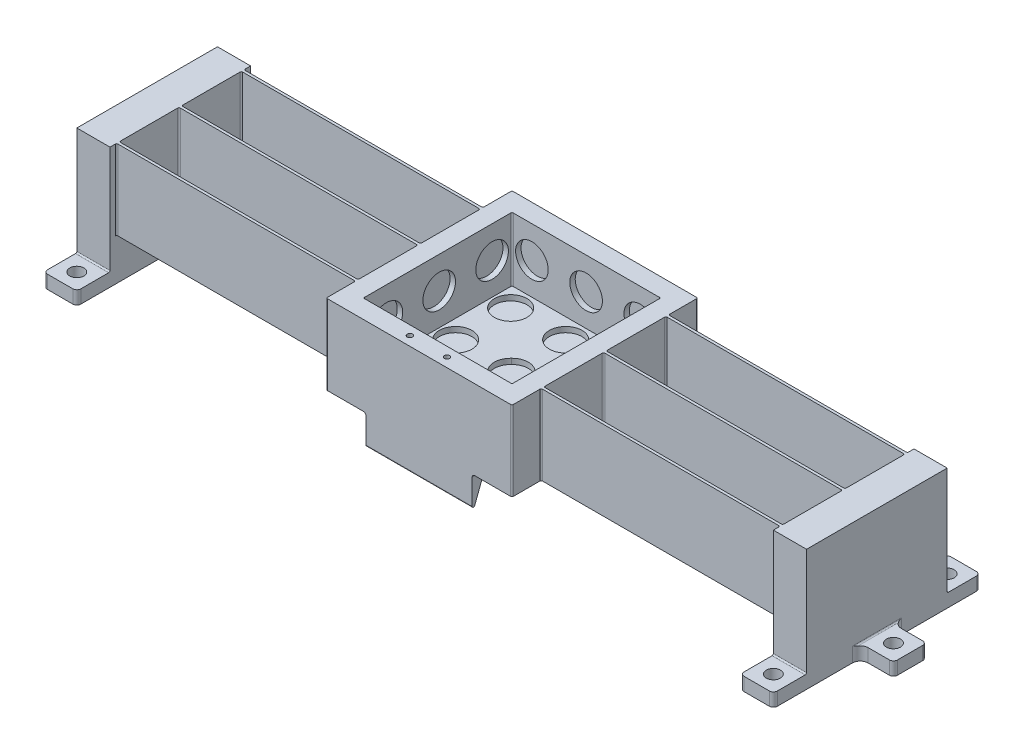
SolidWorks part; units mm, degrees
ref_plane "Front Plane" through (0, 0, 0) normal (0, 0, 1) x (1, 0, 0)
ref_plane "Top Plane" through (0, 0, 0) normal (0, 1, 0) x (1, 0, 0)
ref_plane "Right Plane" through (0, 0, 0) normal (1, 0, 0) x (0, 0, -1)
sketch "Sketch1" plane through (0, 0, 0) normal (0, 1, 0) x (1, 0, 0)
  line L1 (-35, -35) -> (35, -35)
  line L2 (-35, -35) -> (-35, 35)
  line L3 (-35, 35) -> (35, 35)
  line L4 (35, -35) -> (35, 35)
  line L5 (-35, -35) -> (35, 35) construction
  line L6 (-35, 35) -> (35, -35) construction
  point P0 (0, 0)
  dimension "D1" = 70
  dimension "D2" = 70
extrude "Boss-Extrude1" add sketch "Sketch1" along normal blind 30
shell "Shell1" thickness 7 removed face at (0, 30, 0)
sketch "Sketch2" plane through (0, 30, 0) normal (0, 1, 0) x (1, 0, 0)
  line L0 (-35, 35) -> (-35, -35) construction
  line L1 (-28, -28) -> (28, -28) construction
  line L2 (-28, -28) -> (-28, 28) construction
  line L3 (-28, 28) -> (28, 28) construction
  line L4 (28, -28) -> (28, 28) construction
  line L5 (-28, -28) -> (28, 28) construction
  line L6 (-28, 28) -> (28, -28) construction
  line L7 (35, 35) -> (-35, 35) construction
  point P0 (0, 0)
  dimension "D1" = 7
  dimension "D2" = 7
sketch "Sketch3" plane through (35, 0, 0) normal (1, 0, 0) x (0, 0, -1)
  line L0 (-35, 30) -> (35, 30) construction
  line L1 (-24, 30) -> (-23, 30)
  line L2 (-24, 30) -> (-24, 0)
  line L3 (-24, 0) -> (-23, 0)
  line L4 (-23, 30) -> (-23, 0)
  line L5 (-35, 0) -> (35, 0) construction
  line L6 (-28, 30) -> (28, 30) construction
  line L7 (-0.5, 30) -> (0.5, 30)
  line L8 (-0.5, 30) -> (-0.5, 0)
  line L9 (-0.5, 0) -> (0.5, 0)
  line L10 (0.5, 30) -> (0.5, 0)
  line L11 (28, 30) -> (-28, 30) construction
  line L12 (24, 30) -> (23, 30)
  line L13 (24, 30) -> (24, 0)
  line L14 (24, 0) -> (23, 0)
  line L15 (23, 30) -> (23, 0)
  line L16 (-23.5, 30) -> (-23.5, 0) construction
  line L17 (0, 30) -> (0, 0) construction
  line L18 (23.5, 0) -> (23.5, 30) construction
  dimension "D1" = 23
  dimension "D2" = 23
  dimension "D3" = 1
extrude "Boss-Extrude2" add sketch "Sketch3" along normal blind 90
sketch "Sketch5" plane through (125, 0, 0) normal (1, 0, 0) x (0, 0, -1)
  line L0 (-24, 30) -> (-24, 0) construction
  line L1 (-26.5, 30) -> (26.5, 30)
  line L2 (-26.5, 30) -> (-26.5, 0)
  line L3 (-26.5, 0) -> (26.5, 0)
  line L4 (26.5, 30) -> (26.5, 0)
  line L5 (28, 30) -> (-28, 30) construction
  line L6 (24, 0) -> (35, 0) construction
  line L7 (24, 0) -> (24, 30) construction
  dimension "D1" = 2.5
  dimension "D2" = 2.5
extrude "Boss-Extrude3" add sketch "Sketch5" along normal blind 12.5
sketch "Sketch6" plane through (0, 0, 0) normal (0, -1, 0) x (1, 0, 0)
  line L1 (125, 26.5) -> (137.5, 26.5)
  line L2 (125, 26.5) -> (125, -26.5)
  line L3 (125, -26.5) -> (137.5, -26.5)
  line L4 (137.5, 26.5) -> (137.5, -26.5)
extrude "Boss-Extrude4" add sketch "Sketch6" along normal blind 15.75
sketch "Sketch8" plane through (0, -15.75, 0) normal (0, -1, 0) x (1, 0, 0)
  line L1 (137.5, -26.5) -> (125, -26.5)
  line L2 (137.5, -26.5) -> (137.5, -39)
  line L3 (137.5, -39) -> (125, -39)
  line L4 (125, -26.5) -> (125, -39)
  line L5 (137.5, 26.5) -> (125, 26.5)
  line L6 (137.5, 26.5) -> (137.5, 39)
  line L7 (137.5, 39) -> (125, 39)
  line L8 (125, 26.5) -> (125, 39)
  line L13 (137.5, -26.5) -> (137.5, 26.5) construction
  line L14 (150, -6.25) -> (137.5, -6.25)
  line L15 (150, -6.25) -> (150, 6.25)
  line L16 (150, 6.25) -> (137.5, 6.25)
  line L17 (137.5, -6.25) -> (137.5, 6.25)
  line L18 (150, -6.25) -> (137.5, 6.25) construction
  line L19 (150, 6.25) -> (137.5, -6.25) construction
  line L20 (125, 0) -> (150, 0) construction
  line L21 (125, 0.5) -> (125, -0.5) construction
  point P13 (143.75, 0)
  point P19 (137.5, 0)
  point P20 (137.5, 0)
extrude "Boss-Extrude5" add sketch "Sketch8" against normal blind 5
hole_wizard "Ø5.0mm Dowel Hole1" positions "Sketch9" profile "Sketch10" hole size "Ø5.0" standard "ANSI Metric"
sketch "Sketch9" plane through (0, -10.75, 0) normal (0, 1, 0) x (1, 0, 0)
  line L0 (131.25, 39) -> (131.25, 32.75) construction
  line L1 (125, 39) -> (137.5, 39) construction
  line L2 (131.25, 32.75) -> (137.5, 32.75) construction
  line L3 (137.5, 39) -> (137.5, 26.5) construction
  line L5 (137.5, 0) -> (143.75, 0) construction
  line L6 (137.5, -6.25) -> (137.5, 6.25) construction
  line L7 (143.75, 0) -> (143.75, 6.25) construction
  line L8 (137.5, 6.25) -> (150, 6.25) construction
  line L10 (131.25, -26.5) -> (131.25, -32.75) construction
  line L11 (125, -26.5) -> (137.5, -26.5) construction
  line L12 (131.25, -32.75) -> (137.5, -32.75) construction
  line L13 (137.5, -26.5) -> (137.5, -39) construction
  point P0 (131.25, 32.75)
  point P2 (143.75, 0)
  point P4 (131.25, -32.75)
sketch "Sketch10" plane through (131.25, -10.75, -32.75) normal (1, 0, 0) x (0, 0, 1)
  line L0 (0, 0) -> (0, 18.1023)
  line L1 (0, 18.1023) -> (2.65, 16.51)
  line L2 (2.65, 16.51) -> (2.65, 0)
  line L5 (2.65, 0) -> (0, 0)
  line L10 (0, 18.1023) -> (-2.65, 16.51) construction
  line L11 (0, -6.35) -> (0, 107.95) construction
  dimension "Hole Dia." = 5.3
  dimension "Hole Depth" = 16.51
  dimension "Drill Angle" = 118
mirror "Mirror1" about plane through (0, 0, 0) normal (1, 0, 0) of "Boss-Extrude2", "Boss-Extrude3", "Boss-Extrude5", "Boss-Extrude4", "Ø5.0mm Dowel Hole1"
fillet "Fillet1" radius 0.5 30 edges at (35, 15, 23) (125, 15, 23) (35, 15, 24) (125, 15, 24) (35, 15, 0.5) (125, 15, 0.5) (35, 15, -0.5) (125, 15, -0.5) (35, 15, -23) (125, 15, -23) (35, 15, -24) (125, 15, -24) (-125, 15, 24) (-125, 15, 23) (-125, 15, 0.5) (-125, 15, -0.5) (-125, 15, -24) (-125, 15, -23) (-35, 15, 24) (-35, 15, 23) (-35, 15, 0.5) (-35, 15, -0.5) (-35, 15, -23) (-35, 15, -24) (-131.25, -10.75, -26.5) (-137.5, -10.75, 0) (-131.25, -10.75, 26.5) (131.25, -10.75, 26.5) (131.25, -10.75, -26.5) (137.5, -10.75, 0)
fillet "Fillet2" radius 1.5 12 edges at (150, -13.25, 6.25) (150, -13.25, -6.25) (137.5, -13.25, -39) (125, -13.25, -39) (137.5, -13.25, 39) (125, -13.25, 39) (-125, -13.25, -39) (-137.5, -13.25, -39) (-150, -13.25, -6.25) (-150, -13.25, 6.25) (-125, -13.25, 39) (-137.5, -13.25, 39)
sketch "Sketch11" plane through (0, 6, 0) normal (0, 1, 0) x (1, 0, 0)
  line L26 (-28, -28) -> (-28, 28) construction
  line L32 (-28, -28) -> (28, -28) construction
  circle A0 centre (-21, -21) radius 6.15
  dimension "D1" = 12.3
  dimension "D2" = 0.85
  dimension "D3" = 0.85
extrude "Cut-Extrude1" cut sketch "Sketch11" against normal blind 2.05
pattern_linear "LPattern1" count 3 spacing 20.75 along (1, 0, 0) count 3 spacing 20.75 along (0, 0, -1) of "Cut-Extrude1"
sketch "Sketch14" plane through (0, 6, 0) normal (0, 1, 0) x (1, 0, 0)
  line L0 (-28, 0) -> (0, 0) construction
  line L1 (-28, 28) -> (-28, -28) construction
  line L2 (0, 0) -> (0, -28) construction
  line L3 (-28, -28) -> (28, -28) construction
  circle A0 centre (0, 0) radius 6.15
  dimension "D1" = 12.3
extrude "Cut-Extrude4" cut sketch "Sketch14" against normal blind 2.05
sketch "Sketch12" plane through (-28, 0, 0) normal (1, 0, 0) x (0, 0, -1)
  line L5 (-28, 18) -> (-19.35, 18) construction
  line L6 (-28, 30) -> (-28, 6) construction
  circle A0 centre (-19.35, 18) radius 6.15
  dimension "D1" = 12.3
  dimension "D2" = 2.5
extrude "Cut-Extrude2" cut sketch "Sketch12" against normal blind 2.05
pattern_linear "LPattern2" count 3 spacing 19.925 along (0, 0, -1) of "Cut-Extrude2"
sketch "Sketch13" plane through (0, 0, -28) normal (0, 0, -1) x (-1, 0, 0)
  line L6 (-28, 30) -> (-28, 6) construction
  line L7 (-20.35, 18) -> (-28, 18) construction
  circle A0 centre (-20.35, 18) radius 6.15
  dimension "D1" = 12.3
  dimension "D3" = 1.5
extrude "Cut-Extrude3" cut sketch "Sketch13" along normal blind 2.05
pattern_linear "LPattern3" count 3 spacing 20.425 along (-1, 0, 0) of "Cut-Extrude3"
mirror "Mirror2" about plane through (0, 0, 0) normal (1, 0, 0) of "LPattern2", "Cut-Extrude2"
fillet "Fillet3" radius 0.5 4 edges at (28, 18, -28) (-28, 18, -28) (28, 18, 28) (-28, 18, 28)
fillet "Fillet4" radius 0.5 4 edges at (-35, 15, 35) (35, 15, 35) (-35, 15, -35) (35, 15, -35)
sketch "Sketch19" plane through (0, 0, 0) normal (1, 0, 0) x (0, 0, -1)
  line L0 (-30, 0) -> (-35, -13.25)
  line L1 (-35, -13.25) -> (-35, 0)
  line L2 (-35, 0) -> (-30, 0)
  line L3 (0, 0) -> (-30, 0) construction
  line L4 (37.5, -15.75) -> (-37.5, -15.75) construction
  dimension "D1" = 5
  dimension "D2" = 30
  dimension "D3" = 2.5
extrude "Boss-Extrude8" add sketch "Sketch19" along normal mid plane 40
sketch "Sketch20" plane through (0, 0, 0) normal (1, 0, 0) x (0, 0, -1)
  line L0 (-35, 20) -> (-42.5, 20)
  line L1 (-42.5, 20) -> (-42.5, 30)
  line L2 (-26.5, 30) -> (-42.5, 30) construction
  line L5 (-42.5, 30) -> (-40, 30)
  line L6 (-40, 30) -> (-40, 22.5)
  line L7 (-40, 22.5) -> (-35, 22.5)
  line L8 (-35, 22.5) -> (-35, 20)
  line L9 (-35, 30) -> (-35, 0) construction
  line L10 (-35, 0) -> (-35, 30) construction
  dimension "D1" = 5
  dimension "D2" = 10
  dimension "D3" = 2.5
  dimension "D4" = 2.5
extrude "Place For Sensor" [suppressed] add sketch "Sketch20" along normal mid plane 10
fillet "Place For Sensor Fillet5" [suppressed] radius 0.5
fillet "Place For Sensor Fillet6" [suppressed] radius 1.5
hole_wizard "Place For Sensor Ø3.0mm Dowel Hole2" [suppressed] positions "Sketch21" profile "Sketch22" hole size "Ø3.0" standard "ANSI Metric"
sketch "Sketch21" [suppressed] plane through (0, 0, 32.5) normal (0, 0, 1) x (1, 0, 0)
  line L0 (-2.5, 27.5) -> (2.5, 27.5) construction
  line L2 (-18, 30) -> (18, 30) construction
  line L3 (-5, 28.5) -> (-5, 20.5) construction
  line L4 (5, 28.5) -> (5, 20.5) construction
  point P0 (-2.5, 27.5)
  point P2 (2.5, 27.5)
  dimension "D1" = 2.5
  dimension "D2" = 2.5
  dimension "D3" = 2.5
sketch "Sketch22" plane through (-2.5, 27.5, 32.5) normal (1, 0, 0) x (0, -1, 0)
  line L0 (0, 0) -> (0, 2.5)
  line L1 (0, 2.5) -> (1.65, 2.5)
  line L2 (1.65, 2.5) -> (1.65, 0)
  line L5 (1.65, 0) -> (0, 0)
  line L11 (0, -6.35) -> (0, 107.95) construction
  dimension "Thru Hole Dia." = 3.3
  dimension "Thru Hole Depth" = 2.5
sketch "Sketch23" plane through (0, 30, 0) normal (0, 1, 0) x (1, 0, 0)
  line L1 (-28, -28) -> (28, -28) construction
  circle A0 centre (-7, -31.5) radius 1
  circle A1 centre (7, -31.5) radius 1
  dimension "D4" = 2
  dimension "D1" = 3.5
  dimension "D2" = 14
  dimension "D3" = 7
extrude "Cut-Extrude5" cut sketch "Sketch23" against normal blind 6
fillet "Fillet5" radius 0.5 1 edges at (0, -13.25, 35)
fillet "Fillet6" radius 1 3 edges at (-20, 0, 32.5) (20, 0, 32.5) (0, 0, 30)
fillet "Fillet8" radius 3 4 edges at (137.5, -13, 6.25) (137.5, -13, -6.25) (-137.5, -13, -6.25) (-137.5, -13, 6.25)
